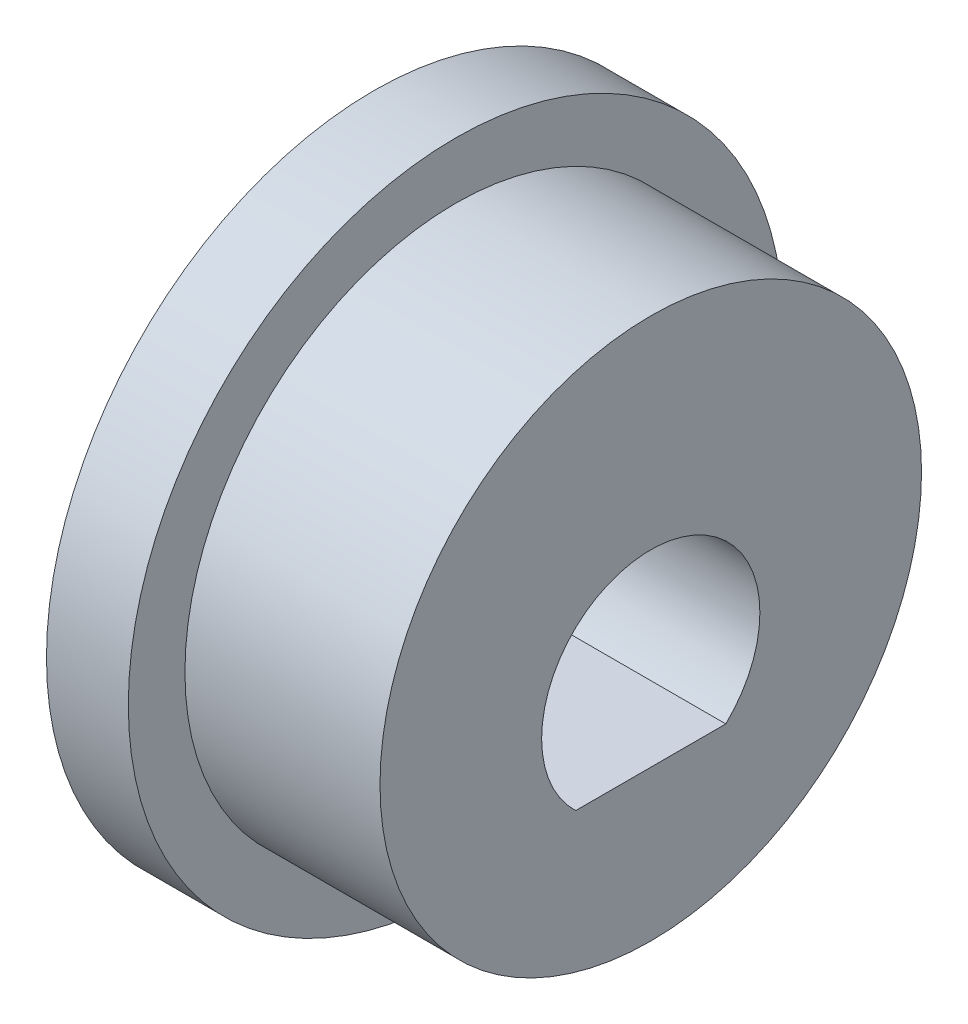
SolidWorks part; units mm, degrees
ref_plane "Ebene vorne" through (0, 0, 0) normal (0, 0, 1) x (1, 0, 0)
ref_plane "Ebene oben" through (0, 0, 0) normal (0, 1, 0) x (1, 0, 0)
ref_plane "Ebene rechts" through (0, 0, 0) normal (1, 0, 0) x (0, 0, -1)
sketch "Skizze1" plane through (0, 0, 0) normal (1, 0, 0) x (0, 0, -1)
  circle A0 centre (0, 1.5) radius 9.925
  point P3 (0, 0)
  point P4 (0, 0.6434)
  point P6 (0, 0)
  point P7 (0, 0)
  dimension "D1" = 19.85
  dimension "D2" = 1.5
extrude "Aufsatz-Linear austragen1" add sketch "Skizze1" along normal blind 7.15
sketch "Skizze2" plane through (0, 0, 0) normal (-1, 0, 0) x (0, 0, 1)
  circle A0 centre (0, 1.5) radius 12
  dimension "D1" = 24
extrude "Aufsatz-Linear austragen2" add sketch "Skizze2" along normal blind 3
sketch "Skizze3" plane through (7.15, 0, 0) normal (1, 0, 0) x (0, 0, -1)
  line L0 (2.75, -2.9047) -> (-2.75, -2.9047)
  arc A0 (2.75, -2.9047) -> (-2.75, -2.9047) centre (0, 0) ccw
  dimension "D1" = 4
  dimension "D2" = 5.5
extrude "Schnitt-Linear austragen1" cut sketch "Skizze3" against normal through all and the other way through all
